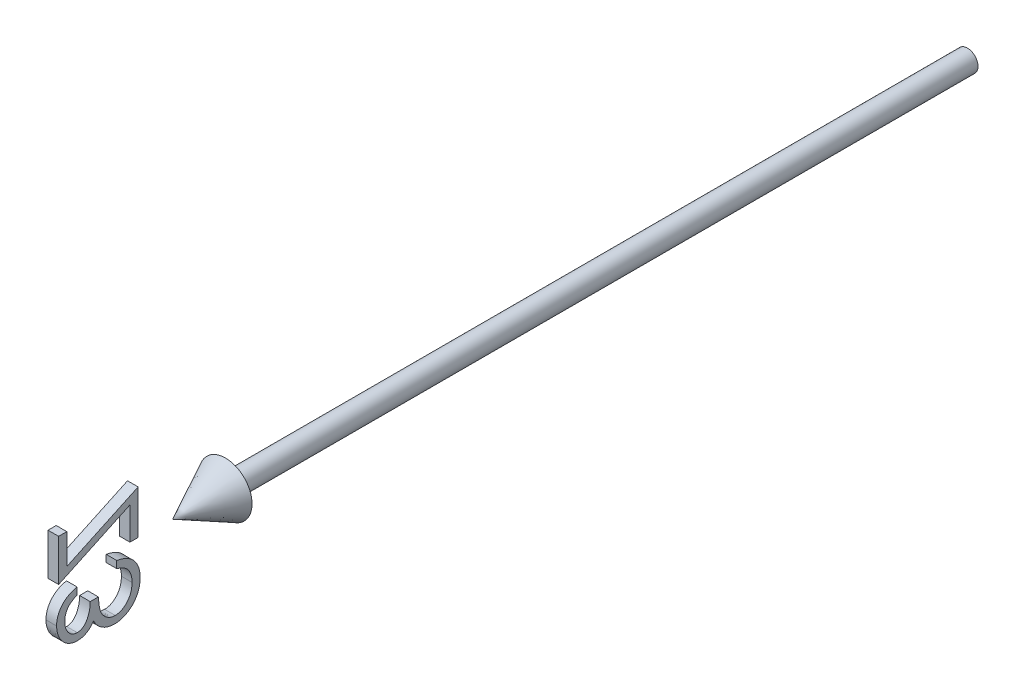
SolidWorks part; units mm, degrees
ref_plane "Front Plane" through (0, 0, 0) normal (0, 0, 1) x (1, 0, 0)
ref_plane "Top Plane" through (0, 0, 0) normal (0, 1, 0) x (1, 0, 0)
ref_plane "Right Plane" through (0, 0, 0) normal (1, 0, 0) x (0, 0, -1)
sketch "Sketch2" plane through (0, 0, 0) normal (0, 1, 0) x (1, 0, 0)
  line L0 (0, 41.95) -> (0, -114.4521) construction
  line L1 (-36.8894, 0) -> (41.4965, 0) construction
  line L2 (0, -150) -> (5, -140)
  line L3 (5, -140) -> (2, -140)
  line L4 (2, -140) -> (2, 0)
  line L5 (2, 0) -> (0, 0)
  line L6 (0, 0) -> (0, -150)
  dimension "D1" = 150
  dimension "D2" = 2
  dimension "D3" = 10
  dimension "D4" = 5
revolve "Revolve1" add sketch "Sketch2" angle 360 about L0
sketch "Sketch3" plane through (0, 0, 0) normal (1, 0, 0) x (0, -1, 0)
  line L0 (0, -101.5706) -> (0, -127.8138) construction
  line L1 (-10.1124, -157.5) -> (14.1256, -157.5) construction
  line L2 (-16.8626, 0) -> (29.5933, 0) construction
  text T0 "Z3" font "Century Gothic" height 15
  dimension "D1" = 157.5
extrude "Boss-Extrude1" add sketch "Sketch3" against normal blind 1 and the other way blind 1 separate body
equation "\"D1@Sketch2\"=\"frame_arrow_length\""
equation "\"D2@Sketch2\"=\"frame_arrow_odA\"/2"
equation "\"D4@Sketch2\"=\"frame_arrow_head_od\""
equation "\"D3@Sketch2\"=\"frame_arrow_head_length\""
equation "\"frame_arrow_length\"=150"
equation "\"frame_arrow_head_length\"=10"
equation "\"frame_arrow_head_od\"=5"
equation "\"frame_arrow_odA\"=4"
equation "\"D1@Sketch3\"=\"frame_arrow_length\"*1.05"
